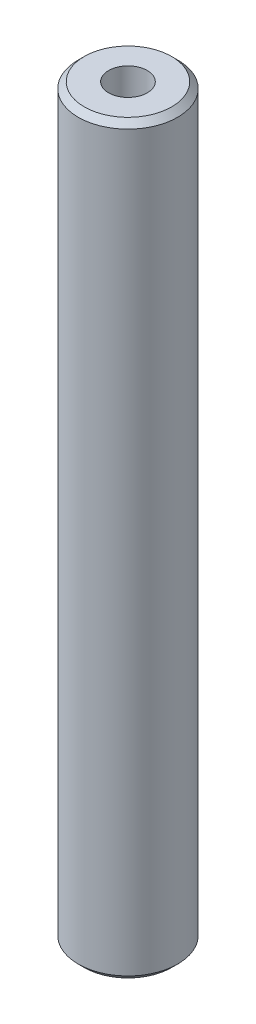
SolidWorks part; units mm, degrees
ref_plane "Front Plane" through (0, 0, 0) normal (0, 0, 1) x (1, 0, 0)
ref_plane "Top Plane" through (0, 0, 0) normal (0, 1, 0) x (1, 0, 0)
ref_plane "Right Plane" through (0, 0, 0) normal (1, 0, 0) x (0, 0, -1)
sketch "Sketch1" plane through (0, 0, 0) normal (0, 1, 0) x (1, 0, 0)
  circle A0 centre (0, 0) radius 40
  dimension "SHAFT_OD" = 80
extrude "Boss-Extrude1" add sketch "Sketch1" along normal blind 600
sketch "Sketch2" plane through (0, 0, 0) normal (0, 1, 0) x (1, 0, 0)
  circle A0 centre (0, 0) radius 15.5748
  dimension "BORE_D" = 31.1496
extrude "Cut-Extrude1" cut sketch "Sketch2" along normal through all
chamfer "Chamfer1" distance 4.8311 angle 45 2 edges at (0, 600, 40) (0, 0, 40)
